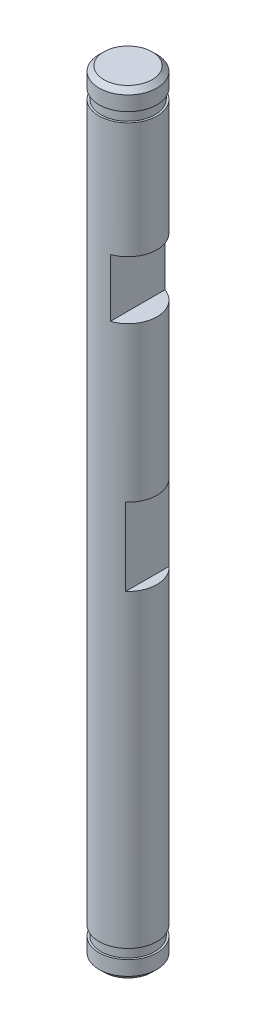
SolidWorks part; units mm, degrees
ref_plane "Alzado" through (0, 0, 0) normal (0, 0, 1) x (1, 0, 0)
ref_plane "Planta" through (0, 0, 0) normal (0, 1, 0) x (1, 0, 0)
ref_plane "Vista lateral" through (0, 0, 0) normal (1, 0, 0) x (0, 0, -1)
sketch "Croquis1" plane through (0, 0, 0) normal (0, 1, 0) x (1, 0, 0)
  circle A0 centre (0, 0) radius 3
  dimension "D1" = 6
extrude "Saliente-Extruir1" add sketch "Croquis1" along normal blind 80
ref_axis "Eje1" through (0, 80, 0) along (0, -1, 0)
sketch "Croquis2" plane through (0, 0, 0) normal (0, 0, 1) x (1, 0, 0)
  line L0 (3, 0) -> (3, 80) construction
  line L1 (2.8, 78) -> (8.3312, 78)
  line L2 (2.8, 78) -> (2.8, 77)
  line L3 (2.8, 77) -> (8.3312, 77)
  line L4 (8.3312, 78) -> (8.3312, 77)
  line L5 (3, 80) -> (-3, 80) construction
  line L6 (-3, 0) -> (3, 0) construction
  line L7 (2.8, 3) -> (8.3312, 3)
  line L8 (2.8, 3) -> (2.8, 2)
  line L9 (2.8, 2) -> (8.3312, 2)
  line L10 (8.3312, 3) -> (8.3312, 2)
  line L11 (3, 0) -> (3, 80) construction
  dimension "D1" = 1
  dimension "D2" = 0.2
  dimension "D3" = 2
  dimension "D4" = 2
  dimension "D5" = 0.2
revolve "Cortar-Revolución1" cut sketch "Croquis2" angle 360 about axis through (0, 80, 0) along (0, -1, 0)
sketch "Croquis3" plane through (0, 0, 0) normal (1, 0, 0) x (0, 0, -1)
  line L1 (-3, 77) -> (-3, 3) construction
  line L3 (-3, 65) -> (3, 65)
  line L4 (-3, 65) -> (-3, 59)
  line L5 (-3, 59) -> (3, 59)
  line L6 (3, 65) -> (3, 59)
  line L7 (3, 3) -> (3, 77) construction
  line L9 (-3, 43) -> (3, 43)
  line L10 (-3, 43) -> (-3, 35)
  line L11 (-3, 35) -> (3, 35)
  line L12 (3, 43) -> (3, 35)
  line L13 (3, 80) -> (-3, 80) construction
  dimension "D1" = 6
  dimension "D2" = 15
  dimension "D3" = 16
  dimension "D4" = 8
extrude "Cortar-Extruir1" cut sketch "Croquis3" along normal up to next from offset 1 contours L6 L3 L4 L5 region at (0, 62, 0)
extrude "Cortar-Extruir3" cut sketch "Croquis3<2>" against normal up to next from offset 2 contours L12 L9 L10 L11 region at (0, 39, 0) offset against normal yes
sketch "Croquis3<2>" plane through (0, 0, 0) normal (1, 0, 0) x (0, 0, -1) same geometry as "Croquis3"
extrude "Cortar-Extruir4" cut sketch "Croquis3<4>" along normal up to next from offset 2 contours L12 L9 L10 L11 region at (0, 39, 0)
sketch "Croquis3<4>" plane through (0, 0, 0) normal (1, 0, 0) x (0, 0, -1) same geometry as "Croquis3"
chamfer "Chaflán1" distance 0.5 angle 45 2 edges at (0, 0, 3) (0, 80, 3)
